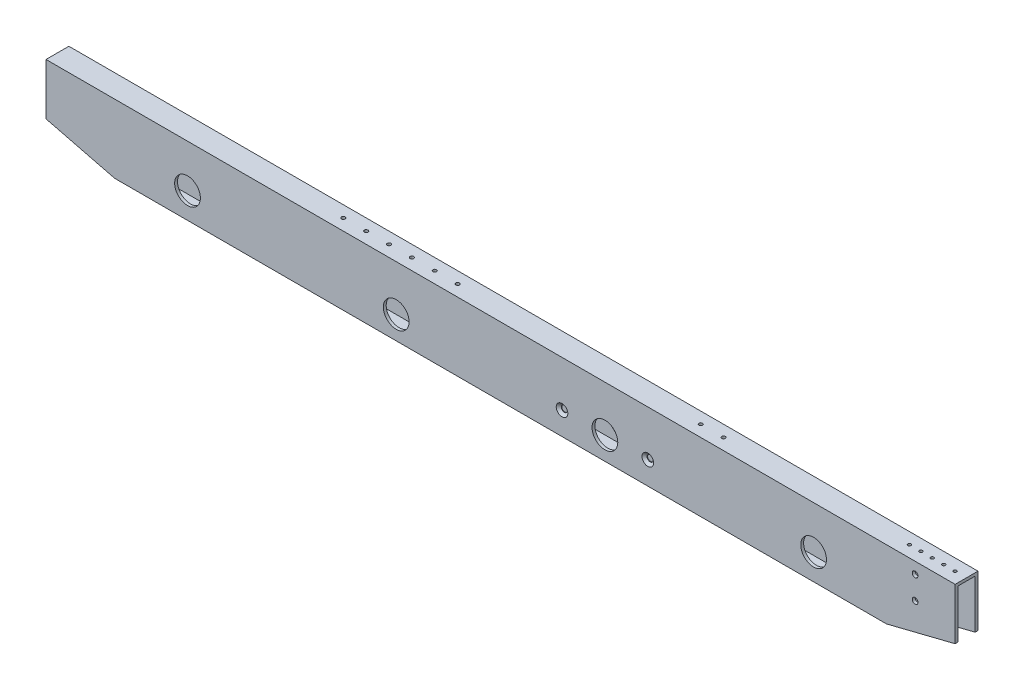
SolidWorks part; units mm, degrees
material "6061-T6 (SS)"
ref_plane "Front Plane" through (0, 0, 0) normal (0, 0, 1) x (1, 0, 0)
ref_plane "Top Plane" through (0, 0, 0) normal (0, 1, 0) x (1, 0, 0)
ref_plane "Right Plane" through (0, 0, 0) normal (1, 0, 0) x (0, 0, -1)
sketch "Sketch1" plane through (0, 0, 0) normal (0, 0, 1) x (1, 0, 0)
  line L0 (0, -12.7) -> (-347.6625, -9.525) construction
  line L1 (-504.825, 38.1) -> (504.825, 38.1)
  line L2 (-504.825, 38.1) -> (-504.825, -38.1)
  line L3 (-504.825, -38.1) -> (504.825, -38.1)
  line L4 (504.825, 38.1) -> (504.825, -38.1)
  line L5 (-504.825, 38.1) -> (504.825, -38.1) construction
  line L6 (-504.825, -38.1) -> (504.825, 38.1) construction
  line L7 (-504.825, -38.1) -> (504.825, -38.1) construction
  line L8 (-504.825, -38.1) -> (-504.825, 12.7) construction
  line L9 (-339.7523, -73.025) -> (358.7477, -73.025) construction
  line L10 (-504.825, 12.7) -> (504.825, 12.7) construction
  line L11 (504.825, -38.1) -> (504.825, 12.7) construction
  line L12 (0, -12.7) -> (347.6625, -9.525) construction
  line L13 (-115.8875, -12.7) -> (115.8875, -12.7) construction
  line L14 (-115.8875, -12.7) -> (115.8875, -12.7) construction
  circle A0 centre (-115.8875, -12.7) radius 14.2875
  circle A1 centre (115.8875, -12.7) radius 14.2875
  circle A2 centre (-347.6625, -9.525) radius 14.2875
  circle A3 centre (347.6625, -9.525) radius 14.2875
  circle A4 centre (-347.6625, -9.525) radius 63.5 construction
  circle A5 centre (-115.8875, -12.7) radius 63.5 construction
  circle A6 centre (115.8875, -12.7) radius 63.5 construction
  circle A7 centre (347.6625, -9.525) radius 63.5 construction
  point P0 (0, 0)
  point P12 (0, -38.1)
  dimension "D5" = 231.775
  dimension "D4" = 50.8
  dimension "D8" = 231.775
  dimension "D9" = 28.575
  dimension "D6" = 28.575
  dimension "D10" = 127
  dimension "D1" = 76.2
  dimension "D2" = 1009.65
  dimension "D3" = 25.4
  dimension "D7" = 231.775
extrude "Boss-Extrude2" add sketch "Sketch1" along normal mid plane 25.4
sketch "Sketch3" plane through (504.825, 0, 0) normal (1, 0, 0) x (0, 0, -1)
  line L8 (9.525, -34.925) -> (9.525, 34.925)
  line L9 (9.525, 34.925) -> (-9.525, 34.925)
  line L10 (-9.525, 34.925) -> (-9.525, -34.925)
  line L11 (-9.525, -34.925) -> (9.525, -34.925)
  line L12 (9.525, -34.925) -> (9.525, 34.925)
  line L13 (9.525, 34.925) -> (-9.525, 34.925)
  line L14 (-9.525, 34.925) -> (-9.525, -34.925)
  line L15 (-9.525, -34.925) -> (9.525, -34.925)
  dimension "D1" = 3.175
extrude "Cut-Extrude2" cut sketch "Sketch3" against normal through all
sketch "Sketch4" plane through (0, 0, 12.7) normal (0, 0, 1) x (1, 0, 0)
  line L0 (-504.825, -38.1) -> (-504.825, -19.05)
  line L1 (-504.825, 38.1) -> (-504.825, -38.1) construction
  line L2 (-504.825, -19.05) -> (-428.625, -38.1)
  line L3 (-504.825, -38.1) -> (504.825, -38.1) construction
  line L4 (-428.625, -38.1) -> (-504.825, -38.1)
  line L5 (0, -38.1) -> (0, 38.1) construction
  line L6 (504.825, 38.1) -> (-504.825, 38.1) construction
  line L7 (428.625, -38.1) -> (504.825, -38.1)
  line L8 (504.825, -38.1) -> (504.825, -19.05)
  line L9 (504.825, -19.05) -> (428.625, -38.1)
  line L11 (504.825, -19.05) -> (504.825, 38.1) construction
  point P15 (0, 0)
  dimension "D1" = 19.05
  dimension "D2" = 57.15
  dimension "D3" = 76.2
  dimension "D4" = 504.825
  dimension "D5" = 14.036
extrude "Cut-Extrude3" cut sketch "Sketch4" against normal through all
sketch "Sketch9" plane through (0, 38.1, 0) normal (0, 1, 0) x (1, 0, 0)
  line L0 (504.825, -12.7) -> (504.825, 12.7) construction
  circle A0 centre (492.125, 0) radius 1.7272
  circle A1 centre (479.425, 0) radius 1.7272
  circle A2 centre (466.725, 0) radius 1.7272
  circle A3 centre (454.025, 0) radius 1.7272
  circle A4 centre (441.325, 0) radius 1.7272
  point P2 (504.825, 0)
  dimension "D1" = 3.4544
  dimension "D2" = 12.7
  dimension "D3" = 4
  dimension "D4" = 2
extrude "Cut-Extrude4" cut sketch "Sketch9" against normal blind 2.54
sketch "Sketch12" plane through (0, 38.1, 0) normal (0, 1, 0) x (1, 0, 0)
  line L0 (-504.825, -12.7) -> (-504.825, 12.7) construction
  circle A0 centre (-187.325, 0) radius 2.0193
  circle A1 centre (-161.925, 0) radius 2.0193
  circle A2 centre (-136.525, 0) radius 2.0193
  circle A3 centre (-111.125, 0) radius 2.0193
  circle A4 centre (-85.725, 0) radius 2.0193
  circle A5 centre (-60.325, 0) radius 2.0193
  point P5 (-28.575, 0)
  point P15 (-504.825, 0)
  dimension "D1" = 4.0386
  dimension "D2" = 317.5
  dimension "D4" = 476.25
  dimension "D3" = 6
extrude "Cut-Extrude7" cut sketch "Sketch12" against normal blind 5.08
hole_wizard "CSK for 1/4 Flat Head Machine Screw (100)2" positions "Sketch16" profile "Sketch15" countersink size "1/4" standard "ANSI Inch" end condition through all
sketch "Sketch16" plane through (0, 0, 12.7) normal (0, 0, 1) x (1, 0, 0)
  circle A0 centre (115.8875, -12.7) radius 14.2875 construction
  point P4 (68.2625, -12.7)
  point P6 (163.5125, -12.7)
  dimension "D1" = 47.625
  dimension "D2" = 47.625
sketch "Sketch15" plane through (68.2625, -12.7, 12.7) normal (1, 0, 0) x (0, -1, 0)
  line L0 (0, 0) -> (0, 25.4)
  line L1 (0, 25.4) -> (3.3782, 25.4)
  line L2 (3.3782, 25.4) -> (3.3782, 2.5682)
  line L3 (3.3782, 2.5682) -> (6.4389, 0)
  line L5 (6.4389, 0) -> (0, 0)
  line L6 (-3.3782, 2.5682) -> (-6.4389, 0) construction
  line L11 (0, -6.35) -> (0, 107.95) construction
  dimension "Thru Hole Dia." = 6.7564
  dimension "Thru Hole Depth" = 25.4
  dimension "Near C'Sink Dia." = 12.8778
  dimension "Near C'Sink Angle" = 100
sketch "Sketch17" plane through (0, -38.1, 0) normal (0, -1, 0) x (-1, 0, 0)
  line L2 (504.825, 9.525) -> (504.825, -9.525) construction
  circle A0 centre (-396.875, 0) radius 1.7272
  circle A1 centre (-320.675, 0) radius 1.7272
  circle A2 centre (-244.475, 0) radius 1.7272
  circle A3 centre (-168.275, 0) radius 1.7272
  circle A4 centre (-92.075, 0) radius 1.7272
  circle A5 centre (-15.875, 0) radius 1.7272
  circle A6 centre (60.325, 0) radius 1.7272
  point P2 (504.825, 0)
  dimension "D1" = 3.4544
  dimension "D2" = 444.5
  dimension "D3" = 7
extrude "Cut-Extrude8" cut sketch "Sketch17" against normal blind 6.35
sketch "Sketch18" plane through (0, 0, -12.7) normal (0, 0, -1) x (-1, 0, 0)
  circle A0 centre (-115.8875, -12.7) radius 17.4625
  dimension "D1" = 34.925
extrude "Cut-Extrude9" cut sketch "Sketch18" against normal blind 3.81
hole_wizard "1/4 (0.25) Diameter Hole1" positions "Sketch20" profile "Sketch19" hole size "1/4" standard "ANSI Inch" end condition through all
sketch "Sketch20" plane through (0, 0, 12.7) normal (0, 0, 1) x (1, 0, 0)
  line L0 (504.825, -19.05) -> (504.825, 38.1) construction
  line L1 (504.825, 38.1) -> (-504.825, 38.1) construction
  point P0 (460.375, 25.4)
  point P2 (460.375, 0)
  dimension "D1" = 25.4
  dimension "D2" = 44.45
  dimension "D3" = 12.7
sketch "Sketch19" plane through (460.375, 25.4, 12.7) normal (1, 0, 0) x (0, -1, 0)
  line L0 (0, 0) -> (0, 25.4)
  line L1 (0, 25.4) -> (3.175, 25.4)
  line L2 (3.175, 25.4) -> (3.175, 0)
  line L5 (3.175, 0) -> (0, 0)
  line L11 (0, -6.35) -> (0, 107.95) construction
  dimension "Thru Hole Dia." = 6.35
  dimension "Thru Hole Depth" = 25.4
hole_wizard "#10-32 Tapped Hole2" positions "Sketch24" profile "Sketch23" tap size "#10-32" standard "ANSI Inch" end condition through all
sketch "Sketch24" plane through (0, 38.1, 0) normal (0, 1, 0) x (1, 0, 0)
  line L0 (504.825, -12.7) -> (504.825, 12.7) construction
  point P0 (234.95, 0)
  point P2 (209.55, 0)
  dimension "D1" = 269.875
  dimension "D2" = 25.4
sketch "Sketch23" plane through (234.95, 38.1, 0) normal (1, 0, 0) x (0, 0, 1)
  line L0 (0, 0) -> (0, 76.2)
  line L1 (0, 76.2) -> (2.0193, 76.2)
  line L2 (2.0193, 76.2) -> (2.0193, 0)
  line L5 (2.0193, 0) -> (0, 0)
  line L11 (0, -6.35) -> (0, 107.95) construction
  dimension "Thread Major Dia." = 4.0386
  dimension "Thru Tap Drill Depth" = 76.2
